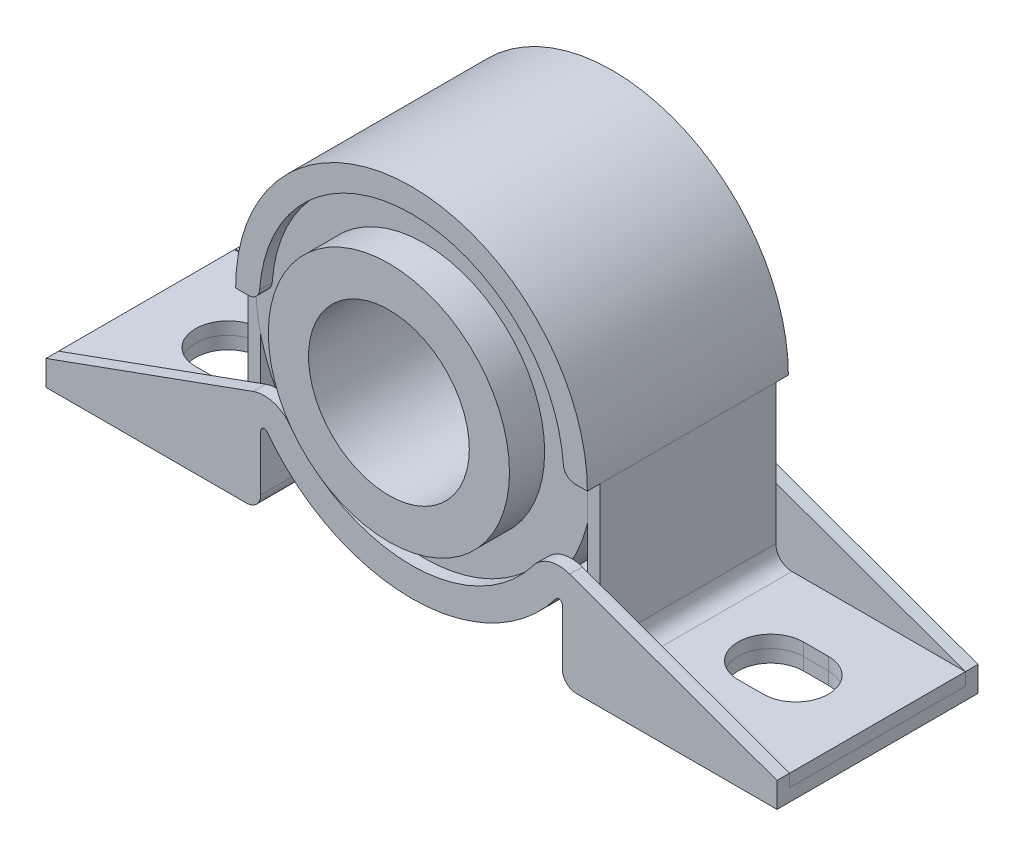
SolidWorks part; units mm, degrees
material "Cast Alloy Steel"
ref_plane "Front" through (0, 0, 0) normal (0, 0, 1) x (1, 0, 0)
ref_plane "Top" through (0, 0, 0) normal (0, 1, 0) x (1, 0, 0)
ref_plane "Right" through (0, 0, 0) normal (1, 0, 0) x (0, 0, -1)
sketch "Sketch1" plane through (0, 0, 0) normal (0, 0, 1) x (1, 0, 0)
  line L1 (-30.3276, -24.6062) -> (-57.7453, -24.6062) construction
  line L2 (-57.7453, -24.6062) -> (-57.7453, -28.575) construction
  line L3 (-57.7453, -28.575) -> (57.7453, -28.575) construction
  line L6 (0, 0) -> (0, -28.575) construction
  line L9 (57.7453, -28.575) -> (57.7453, -24.6063) construction
  line L10 (57.7453, -24.6063) -> (30.3276, -24.6062) construction
  line L12 (-27.7876, 0) -> (-27.7876, -22.0663) construction
  line L13 (-57.7453, -26.5906) -> (-25.8032, -26.5906)
  line L14 (27.7876, 0) -> (27.7876, -22.0662) construction
  line L15 (-25.8032, -26.5906) -> (-25.8032, -17.5333)
  line L16 (25.8032, -17.5333) -> (25.8032, -26.5906)
  line L17 (25.8032, -26.5906) -> (57.7453, -26.5906)
  circle A0 centre (0, 0) radius 12.7 construction
  circle A1 centre (0, 0) radius 19.05 construction
  arc A2 (27.7876, 0) -> (-27.7876, 0) centre (0, 0) ccw construction
  arc A5 (-27.7876, -22.0663) -> (-30.3276, -24.6062) centre (-30.3276, -22.0663) cw construction
  arc A6 (27.7876, -22.0662) -> (30.3276, -24.6062) centre (30.3276, -22.0662) ccw construction
  arc A7 (-25.8032, -17.5333) -> (-21.2348, -16.0045) centre (-23.2632, -17.5333) cw
  arc A8 (-21.2348, -16.0045) -> (21.2348, -16.0045) centre (0, 0) ccw
  arc A9 (21.2348, -16.0045) -> (25.8032, -17.5333) centre (23.2632, -17.5333) cw
  dimension "Shaft Dia" = 25.4
  dimension "K" = 38.1
  dimension "D1" = 2.54
  dimension "w" = 56.3626
  dimension "h" = 28.575
  dimension "g" = 3.9688
  dimension "a" = 115.4906
  dimension "D2" = 1.9844
extrude "Extrude-Thin2" add sketch "Sketch1" along normal mid plane 31.75 thin thin type one direction wall 1.9844
sketch "Sketch4" plane through (0, 0, 15.875) normal (0, 0, 1) x (1, 0, 0)
  line L0 (-57.7453, -24.6062) -> (-24.9915, -12.7563)
  line L1 (24.9915, -12.7563) -> (57.7453, -24.6063)
  line L2 (-30.3276, -24.6062) -> (-57.7453, -24.6062) construction
  line L3 (57.7453, -24.6063) -> (30.3276, -24.6063) construction
  line L10 (26.0572, -28.575) -> (57.7453, -28.575)
  line L11 (57.7453, -28.575) -> (57.7453, -26.5906)
  line L12 (57.7453, -26.5906) -> (26.0572, -26.5906)
  line L13 (25.8032, -26.3366) -> (25.8032, -17.5333)
  line L14 (-25.8032, -17.5333) -> (-25.8032, -26.3366)
  line L15 (-26.0572, -26.5906) -> (-57.7453, -26.5906)
  line L16 (-57.7453, -26.5906) -> (-57.7453, -28.575)
  line L17 (-57.7453, -28.575) -> (-26.0572, -28.575)
  line L18 (-23.8188, -26.3366) -> (-23.8188, -17.5333)
  line L19 (23.8188, -17.5333) -> (23.8188, -26.3366)
  line L20 (26.0572, -28.575) -> (57.7453, -28.575)
  line L21 (57.7453, -28.575) -> (57.7453, -24.6063)
  line L26 (-57.7453, -24.6062) -> (-57.7453, -28.575)
  line L27 (-57.7453, -28.575) -> (-26.0572, -28.575)
  line L28 (-23.8188, -26.3366) -> (-23.8188, -17.5333)
  line L29 (23.8188, -17.5333) -> (23.8188, -26.3366)
  arc A0 (-19.2064, -14.4757) -> (-24.9915, -12.7563) centre (-23.2632, -17.5333) ccw
  arc A1 (24.9915, -12.7563) -> (19.2064, -14.4757) centre (23.2632, -17.5333) ccw
  arc A2 (-19.2064, -14.4757) -> (19.2064, -14.4757) centre (0, 0) ccw
  arc A10 (25.8032, -26.3366) -> (26.0572, -26.5906) centre (26.0572, -26.3366) ccw
  arc A11 (25.8032, -17.5333) -> (21.2348, -16.0045) centre (23.2632, -17.5333) ccw
  arc A12 (-21.2348, -16.0045) -> (21.2348, -16.0045) centre (0, 0) ccw
  arc A13 (-21.2348, -16.0045) -> (-25.8032, -17.5333) centre (-23.2632, -17.5333) ccw
  arc A14 (-26.0572, -26.5906) -> (-25.8032, -26.3366) centre (-26.0572, -26.3366) ccw
  arc A15 (-26.0572, -28.575) -> (-23.8188, -26.3366) centre (-26.0572, -26.3366) ccw
  arc A17 (-22.8195, -17.1989) -> (22.8195, -17.1989) centre (0, 0) ccw
  arc A19 (23.8188, -26.3366) -> (26.0572, -28.575) centre (26.0572, -26.3366) ccw
  arc A21 (-22.8195, -17.1989) -> (-23.8188, -17.5333) centre (-23.2632, -17.5333) ccw
  arc A22 (-22.8195, -17.1989) -> (-23.8188, -17.5333) centre (-23.2632, -17.5333) ccw
  arc A23 (23.8188, -17.5333) -> (22.8195, -17.1989) centre (23.2632, -17.5333) ccw
  arc A24 (23.8188, -17.5333) -> (22.8195, -17.1989) centre (23.2632, -17.5333) ccw
  arc A25 (-26.0572, -28.575) -> (-23.8188, -26.3366) centre (-26.0572, -26.3366) ccw
  arc A27 (-22.8195, -17.1989) -> (22.8195, -17.1989) centre (0, 0) ccw
  arc A29 (23.8188, -26.3366) -> (26.0572, -28.575) centre (26.0572, -26.3366) ccw
  dimension "D2" = 5.08
  dimension "D1" = 0
extrude "Extrude1" add sketch "Sketch4" against normal blind 1.9844
mirror "Mirror1" about plane through (0, 0, 0) normal (0, 0, 1) of "Extrude1"
sketch "Sketch5" plane through (0, 0, 0) normal (0, 0, 1) x (1, 0, 0)
  line L0 (57.7453, -24.6063) -> (30.3276, -24.6062) construction
  line L1 (27.7876, 0) -> (27.7876, -22.0662) construction
  line L2 (-27.7876, 0) -> (-27.7876, -22.0663) construction
  line L3 (-30.3276, -24.6062) -> (-57.7453, -24.6062) construction
  line L4 (57.7453, -24.6063) -> (30.3276, -24.6062)
  line L5 (27.7876, 0) -> (27.7876, -22.0662)
  line L6 (-27.7876, 0) -> (-27.7876, -22.0663)
  line L7 (-30.3276, -24.6062) -> (-57.7453, -24.6062)
  arc A0 (27.7876, -22.0662) -> (30.3276, -24.6062) centre (30.3276, -22.0662) ccw construction
  arc A1 (27.7876, 0) -> (-27.7876, 0) centre (0, 0) ccw construction
  arc A2 (-30.3276, -24.6062) -> (-27.7876, -22.0663) centre (-30.3276, -22.0663) ccw construction
  arc A3 (27.7876, -22.0662) -> (30.3276, -24.6062) centre (30.3276, -22.0662) ccw
  arc A4 (27.7876, 0) -> (-27.7876, 0) centre (0, 0) ccw
  arc A5 (-30.3276, -24.6062) -> (-27.7876, -22.0663) centre (-30.3276, -22.0663) ccw
extrude "Extrude-Thin3" add sketch "Sketch5" along normal up to surface (13.8906 mm away) and the other way up to surface (13.8906 mm away) separate body thin up to face at (0, -21.5538, 13.8906) other way up to face at (0, -21.5538, -13.8906) thin type one direction reverse wall 1.9844
sketch "Sketch6" plane through (0, 0, -13.8906) normal (0, 0, -1) x (-1, 0, 0)
  line L0 (-27.7876, 0) -> (27.7876, 0) construction
  line L1 (-25.8032, 0) -> (-27.7876, 0)
  line L2 (27.7876, 0) -> (25.8032, 0)
  arc A0 (27.7876, 0) -> (-27.7876, 0) centre (0, 0) ccw construction
  arc A1 (27.7876, 0) -> (-27.7876, 0) centre (0, 0) ccw
  arc A2 (-19.2064, -14.4757) -> (19.2064, -14.4757) centre (0, 0) ccw construction
  arc A3 (-19.2064, -14.4757) -> (24.0506, 0) centre (0, 0) ccw construction
  arc A4 (23.9913, 1.6889) -> (-23.9913, 1.6889) centre (0, 0) ccw
  arc A5 (25.8032, 0) -> (-25.8032, 0) centre (0, 0) ccw construction
  arc A6 (25.8032, 0) -> (-25.8032, 0) centre (0, 0) ccw construction
  arc A7 (-25.8032, 0) -> (-23.9913, 1.6889) centre (-25.8032, 1.8165) ccw
  arc A8 (25.8032, 0) -> (23.9913, 1.6889) centre (25.8032, 1.8165) cw
extrude "Extrude2" add sketch "Sketch6" along normal blind 1.9844
mirror "Mirror2" about plane through (0, 0, 0) normal (0, 0, 1) of "Extrude2"
sketch "Sketch7" plane through (0, 0, 0) normal (0, 0, 1) x (1, 0, 0)
  circle A0 centre (0, 0) radius 26.5906
  circle A1 centre (0, 0) radius 19.05
  circle A2 centre (0, 0) radius 19.05 construction
  arc A3 (-21.2348, -16.0045) -> (21.2348, -16.0045) centre (0, 0) ccw construction
extrude "Extrude3" add sketch "Sketch7" along normal up to surface (13.8906 mm away) and the other way up to surface (13.8906 mm away) separate body up to face at (0, -21.5538, 13.8906) other way up to face at (0, -21.5538, -13.8906)
ref_plane "Plane1" through (0, 0, 19.4469) normal (0, 0, -1) x (-1, 0, 0)
sketch "Sketch8" plane through (0, 0, 19.4469) normal (0, 0, 1) x (1, 0, 0)
  circle A0 centre (0, 0) radius 19.05 construction
  circle A1 centre (0, 0) radius 12.7 construction
  circle A2 centre (0, 0) radius 19.05
  circle A3 centre (0, 0) radius 12.7
extrude "Extrude4" add sketch "Sketch8" against normal blind 26.9875 separate body
sketch "Sketch3" plane through (0, 0, 0) normal (0, 1, 0) x (1, 0, 0)
  line L2 (-44.8469, 0) -> (-40.8781, 0) construction
  line L3 (-40.8781, 0) -> (0, 0) construction
  line L4 (0, 0) -> (40.8781, 0) construction
  line L5 (40.8781, 0) -> (44.8469, 0) construction
  line L6 (-44.8469, 5.1594) -> (-40.8781, 5.1594)
  line L7 (-44.8469, -5.1594) -> (-40.8781, -5.1594)
  line L8 (40.8781, -5.1594) -> (44.8469, -5.1594)
  line L9 (44.8469, 5.1594) -> (40.8781, 5.1594)
  arc A0 (-44.8469, 5.1594) -> (-44.8469, -5.1594) centre (-44.8469, 0) ccw
  arc A1 (-40.8781, 5.1594) -> (-40.8781, -5.1594) centre (-40.8781, 0) cw
  arc A2 (40.8781, 5.1594) -> (40.8781, -5.1594) centre (40.8781, 0) ccw
  arc A3 (44.8469, 5.1594) -> (44.8469, -5.1594) centre (44.8469, 0) cw
  point P13 (42.8625, -5.1594)
  point P14 (-42.8625, -5.1594)
  dimension "D1" = 85.725
  dimension "D2" = 40.8781
  dimension "Slot Width" = 10.3187
  dimension "Slot Length" = 14.2875
extrude "Cut-Extrude1" cut sketch "Sketch3" against normal through all
sketch "Sketch9" plane through (0, 0, 0) normal (1, 0, 0) x (0, 0, -1)
  line L0 (-19.4469, 0) -> (7.5406, 0) construction
  line L1 (-19.4469, 19.05) -> (-19.4469, -19.05) construction
  line L2 (7.5406, -12.7) -> (7.5406, 12.7) construction
equation "\"D2@Sketch1\"=\"g@Sketch1\"/2"
equation "\"D5@Extrude-Thin2\"=\"g@Sketch1\"/2"
equation "\"D1@Extrude1\"=\"g@Sketch1\"/2"
equation "\"D5@Extrude-Thin3\" = \"g@Sketch1\"/2"
equation "\"D1@Extrude2\"=\"g@Sketch1\"/2"
